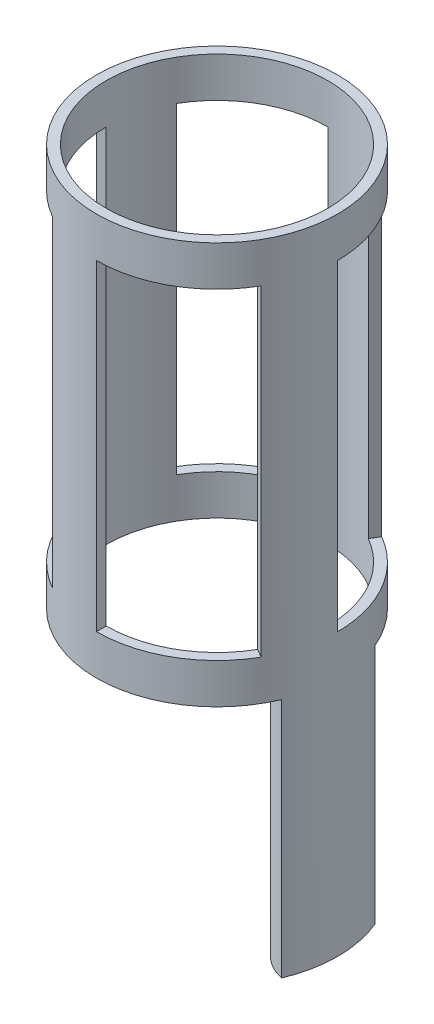
SolidWorks part; units mm, degrees
material "ABS"
ref_plane "Front Plane" through (0, 0, 0) normal (0, 0, 1) x (1, 0, 0)
ref_plane "Top Plane" through (0, 0, 0) normal (0, 1, 0) x (1, 0, 0)
ref_plane "Right Plane" through (0, 0, 0) normal (1, 0, 0) x (0, 0, -1)
sketch "Sketch1" plane through (0, 0, 0) normal (0, 1, 0) x (1, 0, 0)
  line L0 (0, -38.1) -> (0, -35)
  line L1 (0, 35) -> (0, 38.1)
  line L2 (17.5, 30.3109) -> (19.05, 32.9956)
  line L3 (-17.5, -30.3109) -> (-19.05, -32.9956)
  line L4 (35, 0) -> (38.1, 0)
  line L5 (-35, 0) -> (-38.1, 0)
  line L6 (30.3109, -17.5) -> (32.9956, -19.05)
  line L7 (-30.3109, 17.5) -> (-32.9956, 19.05)
  circle A0 centre (0, 0) radius 38.1
  circle A1 centre (0, 0) radius 35
  dimension "D1" = 76.2
  dimension "D2" = 70
  dimension "D3" = 30
  dimension "D4" = 30
extrude "Boss-Extrude1" add sketch "Sketch1" along normal blind 12.7 contours A1 L5 A0 L3 | A1 L7 A0 L5 | A1 L1 A0 L7 | A1 L3 A0 L0 | A1 L0 A0 L6 | A1 L6 A0 L4 | A1 L4 A0 L2 | A1 L2 A0 L1 region at (-9.3578, 0, 34.9236) region at (0.389, 0, 36.55) region at (-32.6587, 0, 18.8555) region at (34.9236, 0, 9.3578) region at (-34.9236, 0, -9.3578) region at (36.55, 0, -0.389) region at (-18.8555, 0, -32.6587) region at (9.3578, 0, -34.9236)
extrude "Boss-Extrude2" add sketch "Sketch1<3>" along normal blind 127 contours A1 L3 A0 L0 | A1 L6 A0 L4 | A1 L2 A0 L1 | A1 L7 A0 L5 region at (-9.3578, 0, 34.9236) region at (34.9236, 0, 9.3578) region at (-34.9236, 0, -9.3578) region at (9.3578, 0, -34.9236)
sketch "Sketch1<3>" plane through (0, 0, 0) normal (0, 1, 0) x (1, 0, 0) same geometry as "Sketch1"
sketch "Sketch2" plane through (0, 127, 0) normal (0, 1, 0) x (1, 0, 0)
  circle A0 centre (0, 0) radius 35
  circle A1 centre (0, 0) radius 38.1
  arc A2 (-32.9956, 19.05) -> (-38.1, 0) centre (0, 0) ccw construction
extrude "Boss-Extrude3" add sketch "Sketch2" against normal blind 12.7
sketch "Sketch3" plane through (0, 0, 0) normal (0, -1, 0) x (1, 0, 0)
  circle A0 centre (0, 0) radius 35
  circle A1 centre (0, 0) radius 38.1
  circle A2 centre (38.1, 0) radius 15
  circle A3 centre (38.1, 0) radius 14
  circle A4 centre (0, 0) radius 35.6
  circle M4 centre (0, 0) radius 35
  circle M5 centre (0, 0) radius 38.1
  dimension "D1" = 30
  dimension "D2" = 28
  dimension "D3" = 2.5
extrude "Boss-Extrude4" add sketch "Sketch3" along normal blind 76.2 contours A3 A2 M4 | A3 A4 A2 M4 | A4 A3 A2 M5 | A4 A3 A1 | A4 A2 A3 M5 | A2 A4 A3 M4 region at (23.8086, 0, 0) region at (32.643, 0, 13.4329) region at (32.643, 0, -13.4329) region at (34.1207, 0, 13.9245) region at (36.008, 0, 0) region at (34.1207, 0, -13.9245)
